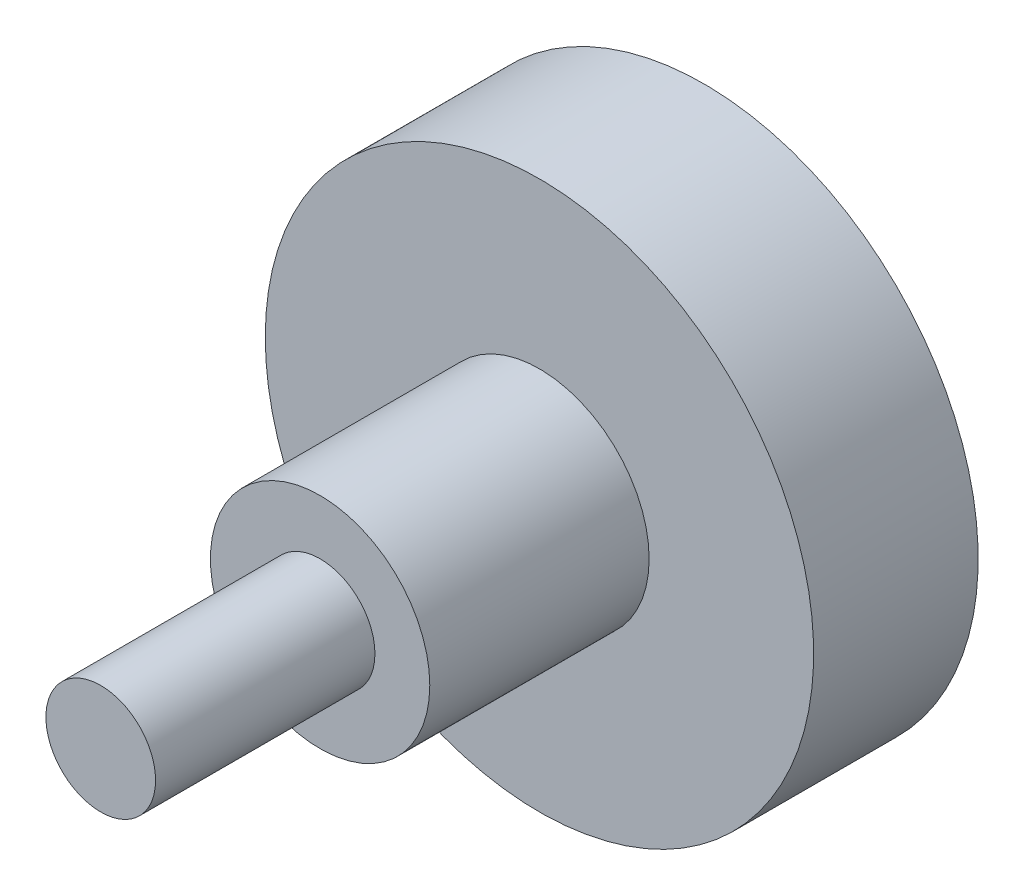
SolidWorks part; units mm, degrees
ref_plane "Front" through (0, 0, 0) normal (0, 0, 1) x (1, 0, 0)
ref_plane "Top" through (0, 0, 0) normal (0, 1, 0) x (1, 0, 0)
ref_plane "Right" through (0, 0, 0) normal (1, 0, 0) x (0, 0, -1)
sketch "Sketch1" plane through (0, 0, 0) normal (0, 0, 1) x (1, 0, 0)
  circle A0 centre (0, 0) radius 15.875
  dimension "D1" = 31.75
extrude "Extrude1" add sketch "Sketch1" along normal blind 9.525
sketch "Sketch2" plane through (0, 0, 9.525) normal (0, 0, 1) x (1, 0, 0)
  circle A0 centre (0, 0) radius 6.35
  dimension "D1" = 12.7
extrude "Extrude2" add sketch "Sketch2" along normal blind 12.7
sketch "Sketch3" plane through (0, 0, 22.225) normal (0, 0, 1) x (1, 0, 0)
  circle A0 centre (0, 0) radius 3.175
  dimension "D1" = 6.35
extrude "Extrude3" add sketch "Sketch3" along normal blind 12.7
